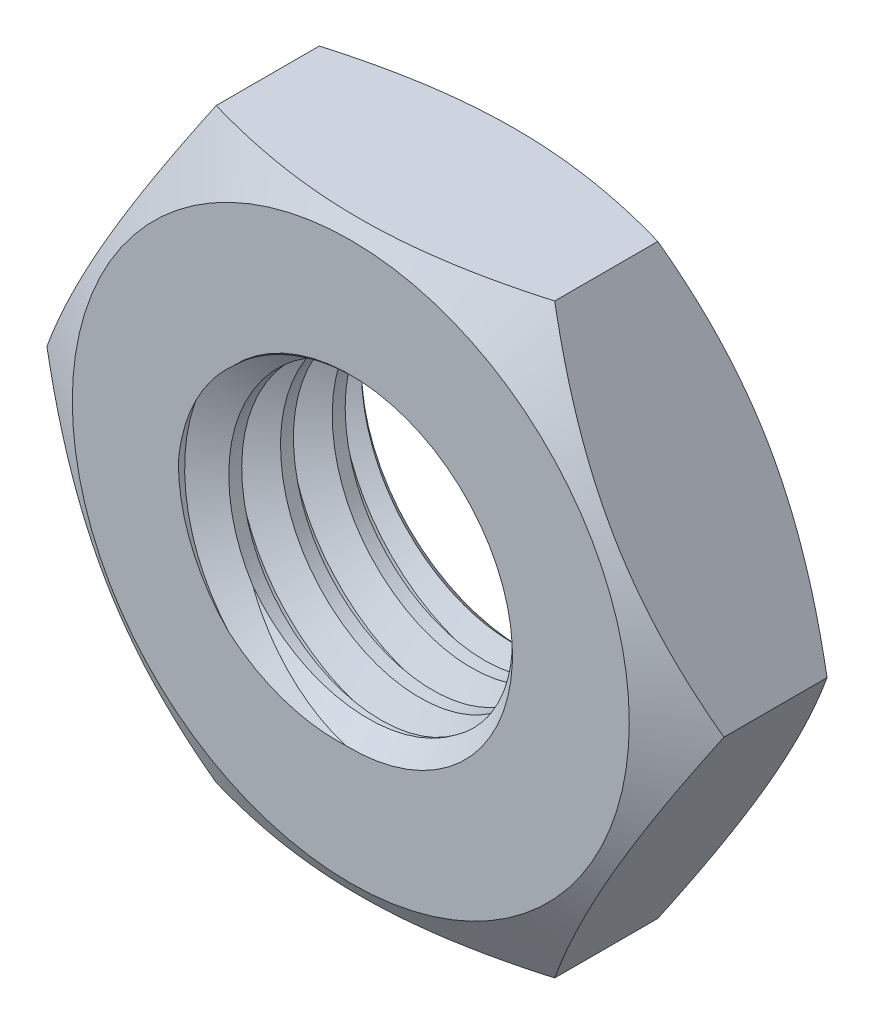
SolidWorks part; units mm, degrees
ref_plane "Plane1" through (0, 0, 0) normal (0, 0, 1) x (1, 0, 0)
ref_plane "Plane2" through (0, 0, 0) normal (0, 1, 0) x (1, 0, 0)
ref_plane "Plane3" through (0, 0, 0) normal (1, 0, 0) x (0, 0, -1)
sketch "BaseNutSke" plane through (0, 0, 0) normal (0, 0, 1) x (1, 0, 0)
  line L6 (4.9075, -8.5) -> (-4.9075, -8.5)
  line L7 (4.9075, 8.5) -> (-4.9075, 8.5)
  line L8 (4.9075, -8.5) -> (9.815, 0)
  line L9 (9.815, 0) -> (4.9075, 8.5)
  line L10 (-4.9075, 8.5) -> (-9.815, 0)
  line L11 (-9.815, 0) -> (-4.9075, -8.5)
  circle A0 centre (0, 0) radius 4.25 construction
  circle A1 centre (0, 0) radius 9.815 construction
  circle A2 centre (0, 0) radius 5
  dimension "Tap_drill" = 8.5
  dimension "Diameter" = 10
  dimension "Width_flats" = 17
extrude "BaseNut" add sketch "BaseNutSke" against normal blind 5
cosmetic thread "ThreadCosmetic" [suppressed] parameters "Thread_major"=10
ref_plane "Plane4" through (0, 0, -2.5) normal (0, 0, -1) x (-1, 0, 0)
sketch "Sketch6" plane through (0, 0, -5) normal (0, 0, -1) x (-1, 0, 0)
  circle A0 centre (0, 0) radius 8.075
  dimension "D1" = 16.15
extrude "Cut-Extrude2" cut sketch "Sketch6" against normal through all draft 60 flip side to cut
mirror "Mirror1" about plane through (0, 0, -2.5) normal (0, 0, -1) of "Cut-Extrude2"
sketch "Эскиз1" plane through (0, 0, 0) normal (0, 0, 1) x (1, 0, 0)
  circle A0 centre (0, 0) radius 5 construction
  circle A1 centre (0, 0) radius 5
curve "Спираль1" pitch 1.5 height 6 radius 5 centre (0, 0, 0) axis (0, 0, -1) start towards (1, 0, 0)
sketch "Эскиз2" plane through (0, 0, 0) normal (0, 1, 0) x (1, 0, 0)
  line L0 (-5, 0) -> (-5, -1.3123)
  line L1 (-5, -1.3123) -> (-4.188, -0.8435)
  line L2 (-4.188, -0.8435) -> (-4.188, -0.4688)
  line L3 (-4.188, -0.4688) -> (-5, 0)
  line L4 (-4.513, -0.2812) -> (-4.513, -1.0312) construction
  line L5 (-5, -0.6562) -> (-5.742, -0.6562) construction
  line L6 (0, 0) -> (0, -0.8555) construction
  line L7 (-5, 0) -> (5, 0) construction
  dimension "D1" = 60
  dimension "D2" = 4.513
  dimension "D3" = 8.376
  dimension "D4" = 0.75
sweep "По траектории1" add profiles "Эскиз2" path "Спираль1"
sketch "Эскиз3" plane through (0, 0, 0) normal (0, 0, 1) x (1, 0, 0)
  circle A0 centre (0, 0) radius 8.075 construction
  circle A1 centre (0, 0) radius 8.075
extrude "Вырез-Вытянуть1" cut sketch "Эскиз3" along normal blind 10
sketch "Эскиз4" plane through (0, 0, -5) normal (0, 0, -1) x (-1, 0, 0)
  circle A0 centre (0, 0) radius 8.075 construction
  circle A1 centre (0, 0) radius 8.075
extrude "Вырез-Вытянуть2" cut sketch "Эскиз4" along normal blind 10
sketch "Эскиз5" plane through (0, 0, 0) normal (1, 0, 0) x (0, 0, -1)
  line L0 (0, 0) -> (5, 0) construction
  line L1 (5.1, 4.188) -> (4.5, 4.188)
  line L3 (4.5, 4.188) -> (5.1, 4.788)
  line L4 (5.1, 4.788) -> (5.1, 4.188)
  line L7 (5, -8.075) -> (5, 8.075) construction
  line L8 (2.5, 0) -> (2.5, 9.9534) construction
  line L9 (-0.1, 4.788) -> (-0.1, 4.188)
  line L10 (0.5, 4.188) -> (-0.1, 4.788)
  line L11 (-0.1, 4.188) -> (0.5, 4.188)
  dimension "D1" = 0.6
  dimension "D2" = 8.376
  dimension "D3" = 0.1
revolve "Вырез-Повернуть1" cut sketch "Эскиз5" angle 360 about L0
equation "\"D1@Sketch3\" = \"Width_flats@BaseNutSke\" /2"
equation "' \"Num_threads@ThdSchPat\" = \"Num_threads@ThdSchPat\" - sgn( \"Num_threads@ThdSchPat\" - 1) '---chamfered tips only---"
equation "\"D1@Sketch6\" = 0.95 * \"Width_flats@BaseNutSke\""
